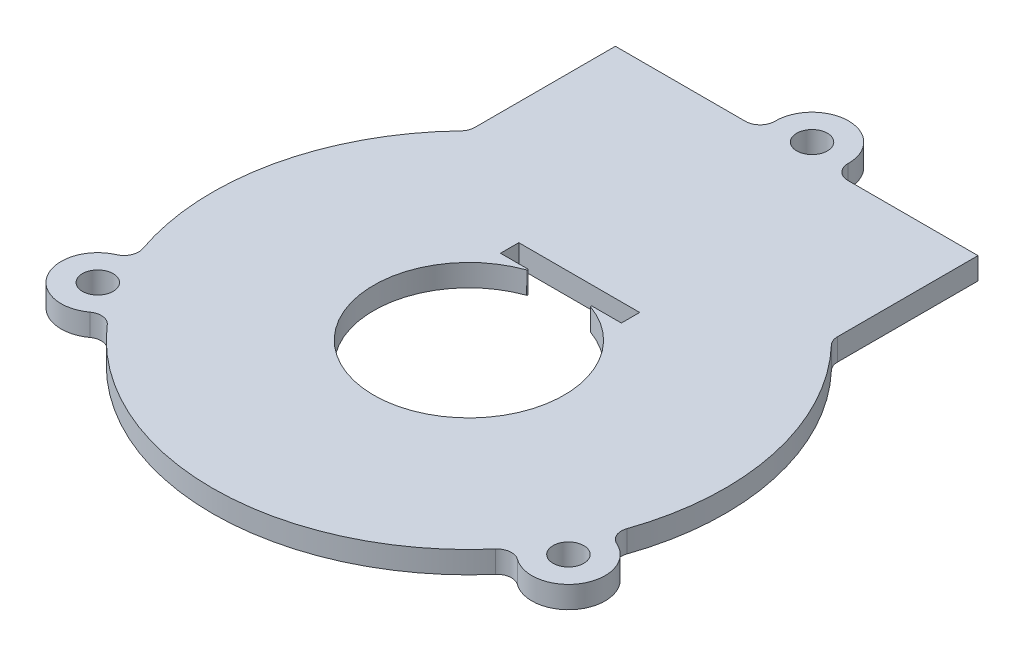
SolidWorks part; units mm, degrees
ref_plane "Front Plane" through (0, 0, 0) normal (0, 0, 1) x (1, 0, 0)
ref_plane "Top Plane" through (0, 0, 0) normal (0, 1, 0) x (1, 0, 0)
ref_plane "Right Plane" through (0, 0, 0) normal (1, 0, 0) x (0, 0, -1)
sketch "Sketch13" plane through (0, 0, 0) normal (0, 1, 0) x (1, 0, 0)
  circle A0 centre (0, 0) radius 35
extrude "Boss-Extrude3" add sketch "Sketch13" along normal blind 3
sketch "Sketch14" plane through (0, 3, 0) normal (0, 1, 0) x (1, 0, 0)
  line L0 (-24.7478, 24.7497) -> (24.7477, 24.7498)
  line L1 (-24.7478, 24.7497) -> (-24.7479, 44.7452)
  line L2 (24.7477, 24.7498) -> (24.7476, 44.7454)
  line L3 (-24.7479, 44.7452) -> (24.7476, 44.7454)
  line L4 (0, 0) -> (60.4611, -34.8658) construction
  line L5 (0, 0) -> (-56.6044, -32.6614) construction
  line L7 (-3.939, 44.1714) -> (-8.8985, 44.1714)
  line L8 (-3.939, 44.1714) -> (-3.939, 47.547)
  line L9 (-3.939, 47.547) -> (-8.8985, 47.547)
  line L10 (-8.8985, 44.1714) -> (-8.8985, 47.547)
  arc A0 (0, 35) -> (-24.7478, 24.7497) centre (0, 0) ccw construction
  circle A1 centre (0, 0) radius 35 construction
  arc A2 (0, 35) -> (-30.3109, -17.4999) centre (0, 0) ccw construction
  arc A3 (0, 35) -> (30.3118, -17.4984) centre (0, 0) ccw
  arc A4 (0, 35) -> (24.7477, 24.7498) centre (0, 0) ccw construction
  circle A5 centre (32.1365, -18.5413) radius 2.1017
  circle A6 centre (32.1365, -18.5413) radius 4.9951
  circle A7 centre (-32.1465, -18.5162) radius 2.0981
  circle A8 centre (-32.1465, -18.5162) radius 4.9995
extrude "Boss-Extrude4" add sketch "Sketch14" against normal up to surface (3 mm away) contours L0 L1 L3 L2 up to face at (0, 0, 35)
sketch "Sketch15" plane through (0, 3, 0) normal (0, 1, 0) x (1, 0, 0)
  line L0 (0, 0) -> (0, 62.3966) construction
  line L1 (-0.0001, 44.7453) -> (0, 46.8414) construction
  line L2 (-24.7479, 44.7452) -> (24.7476, 44.7454) construction
  circle A0 centre (0, 46.8414) radius 2.0961
  circle A1 centre (0, 46.8414) radius 4.996
extrude "Boss-Extrude11" add sketch "Sketch15" against normal up to surface (3 mm away) contours A1 | A0 up to face at (-0.0001, 0, -19.8101)
extrude "Boss-Extrude12" add sketch "Sketch14<6>" against normal up to surface (3 mm away) contours A6 up to face at (0, 0, -29.3038)
sketch "Sketch14<6>" plane through (0, 3, 0) normal (0, 1, 0) x (1, 0, 0) same geometry as "Sketch14"
extrude "Boss-Extrude14" add sketch "Sketch14<8>" against normal through all contours L0 A5 region at (32.1365, 3, 18.5413)
sketch "Sketch14<8>" plane through (0, 3, 0) normal (0, 1, 0) x (1, 0, 0) same geometry as "Sketch14"
hole_wizard "Ø4.2 (4.2) Diameter Hole1" positions "Sketch22" profile "Sketch23" hole size "Ø4.2" standard "ANSI Metric" end condition through all
sketch "Sketch22" plane through (0, 3, 0) normal (0, 1, 0) x (1, 0, 0)
  point P0 (32.1248, -18.5356)
sketch "Sketch23" plane through (32.1248, 3, 18.5356) normal (1, 0, 0) x (0, 0, 1)
  line L0 (0, 0) -> (0, 3)
  line L1 (0, 3) -> (2.1, 3)
  line L2 (2.1, 3) -> (2.1, 0)
  line L5 (2.1, 0) -> (0, 0)
  line L11 (0, -6.35) -> (0, 107.95) construction
  dimension "Thru Hole Dia." = 4.2
  dimension "Thru Hole Depth" = 3
extrude "Boss-Extrude15" add sketch "Sketch14<11>" against normal up to surface (3 mm away) contours A8 up to face at (32.1248, 0, 20.6356)
sketch "Sketch14<11>" plane through (0, 3, 0) normal (0, 1, 0) x (1, 0, 0) same geometry as "Sketch14"
hole_wizard "Ø4.2 (4.2) Diameter Hole2" positions "Sketch26" profile "Sketch27" hole size "Ø4.2" standard "ANSI Metric" end condition through all
sketch "Sketch26" plane through (0, 3, 0) normal (0, 1, 0) x (1, 0, 0)
  point P0 (-32.148, -18.5088)
  point P2 (-32.148, -18.5088)
sketch "Sketch27" plane through (-32.148, 3, 18.5088) normal (1, 0, 0) x (0, 0, 1)
  line L0 (0, 0) -> (0, 3)
  line L1 (0, 3) -> (2.1, 3)
  line L2 (2.1, 3) -> (2.1, 0)
  line L5 (2.1, 0) -> (0, 0)
  line L11 (0, -6.35) -> (0, 107.95) construction
  dimension "Thru Hole Dia." = 4.2
  dimension "Thru Hole Depth" = 3
fillet "Fillet4" radius 2 1 edges at (-24.7478, 1.5, -24.7497)
fillet "Fillet6" radius 2 1 edges at (-32.2839, 1.5, 13.5185)
fillet "Fillet7" radius 2 1 edges at (-27.8924, 1.5, 21.1427)
fillet "Fillet8" radius 2 1 edges at (27.8812, 1.5, 21.1574)
fillet "Fillet9" radius 2 1 edges at (32.2715, 1.5, 13.548)
fillet "Fillet10" radius 2 1 edges at (24.7477, 1.5, -24.7498)
fillet "Fillet11" radius 2 1 edges at (4.535, 1.5, -44.7453)
fillet "Fillet12" radius 2 1 edges at (-4.535, 1.5, -44.7453)
sketch "Sketch28" plane through (0, 3, 0) normal (0, 1, 0) x (1, 0, 0)
  circle A0 centre (0, 0) radius 5
extrude "Cut-Extrude1" cut sketch "Sketch28" against normal up to surface (3 mm away) up to face at (-32.148, 0, 20.6088)
sketch "Sketch29" plane through (0, 3, 0) normal (0, 1, 0) x (1, 0, 0)
  circle A0 centre (0, 0) radius 13
extrude "Cut-Extrude2" cut sketch "Sketch29" against normal up to surface (3 mm away) contours A0 up to face at (0, 0, 5)
sketch "Sketch30" plane through (0, 3, 0) normal (0, 1, 0) x (1, 0, 0)
  line L1 (8.3778, 12.4336) -> (-8.1222, 12.4336)
  line L2 (8.3778, 12.4336) -> (8.3778, 14.9336)
  line L3 (8.3778, 14.9336) -> (-8.1222, 14.9336)
  line L4 (-8.1222, 12.4336) -> (-8.1222, 14.9336)
  dimension "D1" = 16.5
  dimension "D2" = 2.5
extrude "Cut-Extrude5" cut sketch "Sketch30" against normal up to surface (3 mm away) contours L2 L1 L4 L3 up to face at (0, 0, 13)
fillet "Fillet17" radius 0.1 2 edges at (3.7955, 1.5, -12.4336) (-3.7955, 1.5, -12.4336)
